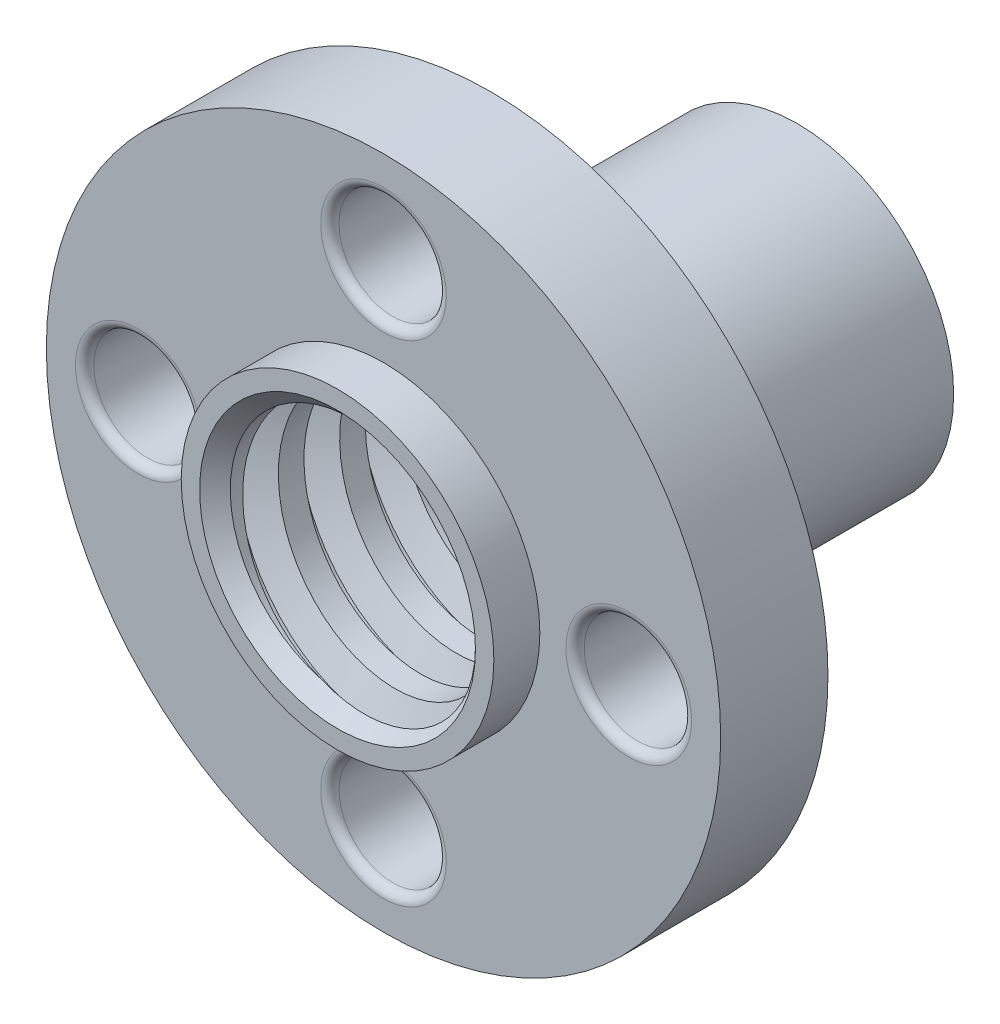
SolidWorks part; units mm, degrees
material "Brass"
ref_plane "Front Plane" through (0, 0, 0) normal (0, 0, 1) x (1, 0, 0)
ref_plane "Top Plane" through (0, 0, 0) normal (0, 1, 0) x (1, 0, 0)
ref_plane "Right Plane" through (0, 0, 0) normal (1, 0, 0) x (0, 0, -1)
sketch "Sketch1" plane through (0, 0, 0) normal (0, 0, 1) x (1, 0, 0)
  circle A0 centre (0, 0) radius 11
  circle A1 centre (0, 0) radius 5.1
  circle A2 centre (0, 0) radius 8 construction
  circle A3 centre (0, 8) radius 1.75
  circle A4 centre (8, 0) radius 1.75
  circle A5 centre (0, -8) radius 1.75
  circle A6 centre (-8, 0) radius 1.75
  point P16 (0, 0)
  dimension "D1" = 22
  dimension "D2" = 10.2
  dimension "D3" = 16
  dimension "D4" = 3.5
  dimension "D5" = 4
extrude "Boss-Extrude1" add sketch "Sketch1" against normal blind 3.5
sketch "Sketch2" plane through (0, 0, 0) normal (0, 0, 1) x (1, 0, 0)
  circle A0 centre (0, 0) radius 5.1
  circle A1 centre (0, 0) radius 4
  dimension "D1" = 8
extrude "Boss-Extrude2" add sketch "Sketch2" along normal blind 1.5 and the other way blind 13.5
sketch "Sketch3" plane through (0, 0, 1.5) normal (0, 0, 1) x (1, 0, 0)
  circle A0 centre (0, 0) radius 4
curve "Helix/Spiral1" pitch 2 height 17 turns 8.5
chamfer "Chamfer1" distance 0.5 angle 45 2 edges at (4, 0, -13.5) (4, 0, 1.5)
sketch "Sketch4" plane through (0, 0, 0) normal (0, 1, 0) x (1, 0, 0)
  line L0 (3, 13.95) -> (3, 12.05)
  line L1 (3, 12.05) -> (5, 12.7854)
  line L2 (5, 12.7854) -> (5, 13.2146)
  line L3 (5, 13.2146) -> (3, 13.95)
  line L4 (3, 13) -> (5, 13)
  point P6 (4, 13)
  dimension "D1" = 1.9
  dimension "D2" = 2
  dimension "D3" = 69.811
sweep "Cut-Sweep1" cut profiles "Sketch4" path "Helix/Spiral1"
fillet "Fillet2" radius 0.3 4 edges at (9.75, 0, 0) (1.75, -8, 0) (-6.25, 0, 0) (1.75, 8, 0)
